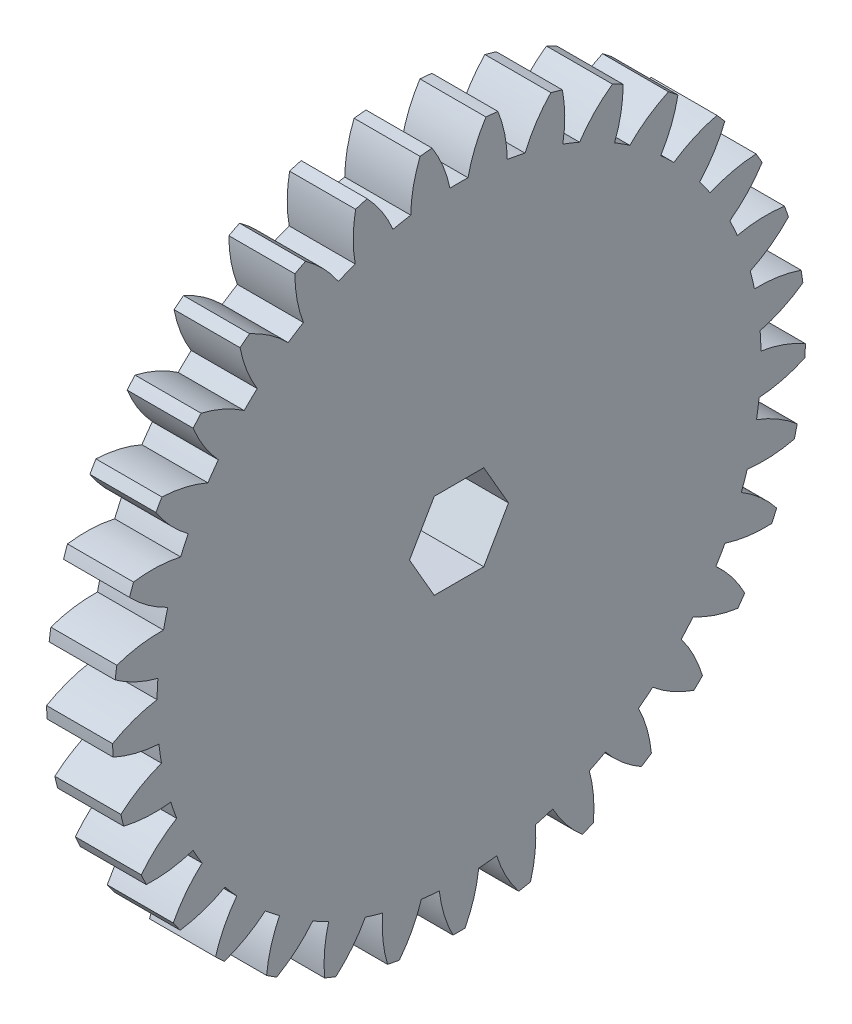
SolidWorks part; units mm, degrees
ref_plane "Plane1" through (0, 0, 0) normal (0, 0, 1) x (1, 0, 0)
ref_plane "Plane2" through (0, 0, 0) normal (0, 1, 0) x (1, 0, 0)
ref_plane "Plane3" through (0, 0, 0) normal (1, 0, 0) x (0, 0, -1)
sketch "HoldingSke" plane through (0, 0, 0) normal (0, 1, 0) x (1, 0, 0)
  line L0 (0, 0) -> (0.5591, -0.3631)
  line L1 (-15, 0) -> (100, 0) construction
  line L2 (0, 0) -> (-2.1039, 2.3779)
  line L3 (0, 0) -> (-11.863, 4.5341)
  line L4 (0, 0) -> (7.2428, 4.7035)
  line L5 (0, 0) -> (-46.8476, -17.4728)
  line L6 (0, 0) -> (-4.1448, -2.7965)
  line L7 (-2.1039, 2.3779) -> (8.6586, 51.2059)
  line L8 (-76.2, 54.61) -> (-75.3, 54.61)
  line L9 (-71.009, 38.7566) -> (-53.1078, 45.2721)
  line L10 (-76.2, 71.12) -> (104.1128, 71.12)
  line L11 (0, 0) -> (-5, 0)
  line L12 (-76.2, 101.6) -> (-76.147, 101.6)
  line L13 (24.9733, 27.94) -> (52.9518, 28.4284)
  line L14 (24.9733, 27.94) -> (24.9743, 27.94)
  line L15 (24.9733, 27.94) -> (100.4006, 29.5858)
  line L16 (-63.627, -1.5) -> (-12.827, -1.5)
  circle A0 centre (0, 0) radius 2.5
  circle A1 centre (0, 0) radius 22.874
  circle A2 centre (0, 0) radius 37.5
  circle A3 centre (0, 0) radius 2.5
  dimension "MHD" = 45.748
  dimension "Hub_dia" = 75
  dimension "Bore" = 5
  dimension "MBD" = 5
  dimension "Num_teeth" = 33
  dimension "Pitch" = 0.6667
  dimension "Overall_len" = 50
  dimension "Show_teeth" = 33
  dimension "Thickness" = 5
  dimension "OAL" = 50.0001
  dimension "T_dim" = 0.9
  dimension "Ap" = 20
  dimension "H" = 19.05
  dimension "Pitch_radius" = 180.3128
  dimension "Width" = 5
  dimension "Backlash" = 0.053
  dimension "Addendum_fac" = 1
  dimension "Dedendum_fac" = 1.25
  dimension "Clearance_fac" = 0.25
  dimension "Dedendum_add" = 0.001
  dimension "Module" = 1.5
sketch "BasProSke" plane through (0, 0, 0) normal (0, 1, 0) x (1, 0, 0)
  line L0 (-10, 0) -> (60, 0) construction
  line L1 (0, 0) -> (0, 26.25)
  line L2 (0, 0) -> (5, 0)
  line L3 (5, 0) -> (5, 26.25)
  line L4 (5, 26.25) -> (0, 26.25)
  dimension "Thickness" = 5
  dimension "Diameter" = 52.5
revolve "Base-Revolve" add sketch "BasProSke" angle 360 about L0
sketch "TooCutSke" plane through (0, 0, 0) normal (1, 0, 0) x (0, 0, -1)
  line L1 (0, 0) -> (0, 107) construction
  line L2 (0, 0) -> (-1.2704, 24.7174) construction
  line L3 (0, 0) -> (-4.7008, 49.2285) construction
  line L4 (-1.2704, 24.7174) -> (-2.3504, 24.6142) construction
  arc A0 (0.6837, 22.8638) -> (-0.6837, 22.8638) centre (0, 0) ccw
  arc A1 (2.0575, 26.1947) -> (-2.0575, 26.1947) centre (0, 0) ccw
  circle A2 centre (0, 0) radius 24.75 construction
  circle A3 centre (0, 0) radius 23.2574 construction
  arc A4 (-0.6837, 22.8638) -> (-2.0575, 26.1947) centre (-10.3699, 20.8176) ccw
  arc A5 (2.0575, 26.1947) -> (0.6837, 22.8638) centre (10.3699, 20.8176) ccw
  dimension "Root_dia" = 45.748
  dimension "Overcut_dia" = 52.5508
  dimension "Pitch_dia" = 49.5
  dimension "Base_dia" = 46.5148
  dimension "Flank_rad" = 9.9
  dimension "Half_ang" = 5.455
  dimension "Half_CT" = 1.0849
extrude "ToothCut" cut sketch "TooCutSke" along normal through all
fillet "Breaks" [suppressed] radius 0.03 tangent propagation no
fillet "RootFillets" [suppressed] radius 0.376
pattern_circular "TeethCuts" count 33 every 10.909 about axis through (-10, 0, 0) along (1, 0, 0) of "ToothCut", "RootFillets", "Breaks"
sketch "HubNeaOneSke" plane through (0, 0, 0) normal (-1, 0, 0) x (0, 0, 1)
  circle A0 centre (0, 0) radius 22.874
  dimension "Diameter" = 45.748
extrude "HubNearOne" [suppressed] add sketch "HubNeaOneSke" along normal blind 45.0001
sketch "HubNeaBotSke" plane through (0, 0, 0) normal (-1, 0, 0) x (0, 0, 1)
  circle A0 centre (0, 0) radius 22.874
  dimension "Diameter" = 45.748
extrude "HubNearBoth" [suppressed] add sketch "HubNeaBotSke" along normal blind 22.5
ref_plane "FarPln" through (5, 0, 0) normal (1, 0, 0) x (0, 0, -1)
sketch "HubFarSke" plane through (5, 0, 0) normal (1, 0, 0) x (0, 0, -1)
  circle A0 centre (0, 0) radius 22.874
  dimension "Diameter" = 45.748
extrude "HubFar" [suppressed] add sketch "HubFarSke" along normal blind 22.5
sketch "BorSke" plane through (0, 0, 0) normal (1, 0, 0) x (0, 0, -1)
  line L1 (-3.75, 0) -> (-1.875, -3.2476)
  line L2 (-1.875, -3.2476) -> (1.875, -3.2476)
  line L3 (1.875, -3.2476) -> (3.75, 0)
  line L4 (3.75, 0) -> (1.875, 3.2476)
  line L5 (1.875, 3.2476) -> (-1.875, 3.2476)
  line L6 (-1.875, 3.2476) -> (-3.75, 0)
  circle A0 centre (0, 0) radius 3.75 construction
  circle A1 centre (0, 0) radius 3.2476 construction
  dimension "Diameter" = 7.5
extrude "Bore" cut sketch "BorSke" along normal mid plane 100.0001
sketch "KeySke" plane through (0, 0, 0) normal (1, 0, 0) x (0, 0, -1)
  line L0 (-1, 0) -> (-1, 3.4)
  line L1 (-1, 3.4) -> (1, 3.4)
  line L2 (1, 3.4) -> (1, 0)
  line L3 (0, 0) -> (0, 34) construction
  line L4 (-1, 0) -> (1, 0)
  dimension "Offset" = 3.4
  dimension "Width" = 2
extrude "Keyway" [suppressed] cut sketch "KeySke" along normal mid plane 100.0001
pattern_circular "Keyway2" [suppressed] count 2 every 90 about axis through (-10, 0, 0) along (1, 0, 0) reverse direction yes
sketch "Sketch1" plane through (0, 0, 0) normal (-1, 0, 0) x (0, 0, 1)
  line L0 (-1.875, -3.2476) -> (1.875, -3.2476) construction
  line L1 (-3.75, 0) -> (-1.875, -3.2476) construction
  line L2 (-1.875, 3.2476) -> (-3.75, 0) construction
  line L3 (1.875, 3.2476) -> (-1.875, 3.2476) construction
  line L4 (3.75, 0) -> (1.875, 3.2476) construction
  line L5 (1.875, -3.2476) -> (3.75, 0) construction
  line L6 (3.75, 0) -> (1.875, 3.2476)
  line L7 (1.875, 3.2476) -> (-1.875, 3.2476)
  line L8 (-1.875, 3.2476) -> (-3.75, 0)
  line L9 (-3.75, 0) -> (-1.875, -3.2476)
  line L10 (-1.875, -3.2476) -> (1.875, -3.2476)
  line L11 (1.875, -3.2476) -> (3.75, 0)
  arc A80 (0.1868, -8.9981) -> (0.8757, -5.5554) centre (-1.8542, -6.7994) ccw
  arc A81 (-0.1868, -8.9981) -> (0.1868, -8.9981) centre (0, 0) ccw
  arc A82 (-0.8757, -5.5554) -> (-0.1868, -8.9981) centre (1.8542, -6.7994) ccw
  arc A83 (-2.5569, -5.0091) -> (-0.8757, -5.5554) centre (0, 0) ccw
  arc A84 (-5.1378, -7.3894) -> (-2.5569, -5.0091) centre (-5.4967, -4.4109) ccw
  arc A85 (-5.4401, -7.1698) -> (-5.1378, -7.3894) centre (0, 0) ccw
  arc A86 (-3.9738, -3.9797) -> (-5.4401, -7.1698) centre (-2.4965, -6.5907) ccw
  arc A87 (-5.0129, -2.5496) -> (-3.9738, -3.9797) centre (0, 0) ccw
  arc A88 (-8.4999, -2.9582) -> (-5.0129, -2.5496) centre (-7.0396, -0.3377) ccw
  arc A89 (-8.6154, -2.6029) -> (-8.4999, -2.9582) centre (0, 0) ccw
  arc A90 (-5.5541, -0.8839) -> (-8.6154, -2.6029) centre (-5.8936, -3.8646) ccw
  arc A91 (-5.5541, 0.8839) -> (-5.5541, -0.8839) centre (0, 0) ccw
  arc A92 (-8.6154, 2.6029) -> (-5.5541, 0.8839) centre (-5.8936, 3.8646) ccw
  arc A93 (-8.4999, 2.9582) -> (-8.6154, 2.6029) centre (0, 0) ccw
  arc A94 (-5.0129, 2.5496) -> (-8.4999, 2.9582) centre (-7.0396, 0.3377) ccw
  arc A95 (-3.9738, 3.9797) -> (-5.0129, 2.5496) centre (0, 0) ccw
  arc A96 (-5.4401, 7.1698) -> (-3.9738, 3.9797) centre (-2.4965, 6.5907) ccw
  arc A97 (-5.1378, 7.3894) -> (-5.4401, 7.1698) centre (0, 0) ccw
  arc A98 (-2.5569, 5.0091) -> (-5.1378, 7.3894) centre (-5.4967, 4.4109) ccw
  arc A99 (-0.8757, 5.5554) -> (-2.5569, 5.0091) centre (0, 0) ccw
  arc A100 (-0.1868, 8.9981) -> (-0.8757, 5.5554) centre (1.8542, 6.7994) ccw
  arc A101 (0.1868, 8.9981) -> (-0.1868, 8.9981) centre (0, 0) ccw
  arc A102 (0.8757, 5.5554) -> (0.1868, 8.9981) centre (-1.8542, 6.7994) ccw
  arc A103 (2.5569, 5.0091) -> (0.8757, 5.5554) centre (0, 0) ccw
  arc A104 (5.1378, 7.3894) -> (2.5569, 5.0091) centre (5.4967, 4.4109) ccw
  arc A105 (5.4401, 7.1698) -> (5.1378, 7.3894) centre (0, 0) ccw
  arc A106 (3.9738, 3.9797) -> (5.4401, 7.1698) centre (2.4965, 6.5907) ccw
  arc A107 (5.0129, 2.5496) -> (3.9738, 3.9797) centre (0, 0) ccw
  arc A108 (8.4999, 2.9582) -> (5.0129, 2.5496) centre (7.0396, 0.3377) ccw
  arc A109 (8.6154, 2.6029) -> (8.4999, 2.9582) centre (0, 0) ccw
  arc A110 (5.5541, 0.8839) -> (8.6154, 2.6029) centre (5.8936, 3.8646) ccw
  arc A111 (5.5541, -0.8839) -> (5.5541, 0.8839) centre (0, 0) ccw
  arc A112 (8.6154, -2.6029) -> (5.5541, -0.8839) centre (5.8936, -3.8646) ccw
  arc A113 (8.4999, -2.9582) -> (8.6154, -2.6029) centre (0, 0) ccw
  arc A114 (5.0129, -2.5496) -> (8.4999, -2.9582) centre (7.0396, -0.3377) ccw
  arc A115 (3.9738, -3.9797) -> (5.0129, -2.5496) centre (0, 0) ccw
  arc A116 (5.4401, -7.1698) -> (3.9738, -3.9797) centre (2.4965, -6.5907) ccw
  arc A117 (5.1378, -7.3894) -> (5.4401, -7.1698) centre (0, 0) ccw
  arc A118 (2.5569, -5.0091) -> (5.1378, -7.3894) centre (5.4967, -4.4109) ccw
  arc A119 (0.8757, -5.5554) -> (2.5569, -5.0091) centre (0, 0) ccw
extrude "Boss-Extrude1" add sketch "Sketch1" along normal blind 6
equation "' \"Module@HoldingSke\" = 6.35"
equation "' \"Num_teeth@HoldingSke\" = 12"
equation "' \"Ap@HoldingSke\" =  20"
equation "' \"Ap@HoldingSke\" = 20"
equation "' \"Width@HoldingSke\" = 0.5 * 25.4"
equation "' \"Hub_dia@HoldingSke\"= 1 * 25.4"
equation "' \"Hub_dia@HoldingSke\" = 1 * 25.4"
equation "' \"Overall_len@HoldingSke\" = 1.0 * 25.4"
equation "' \"Bore@HoldingSke\" = 0.75 * 25.4"
equation "' \"T_dim@HoldingSke\" = 0.1 * 25.4"
equation "' \"Width@KeySke\" = 0.25 * 25.4"
equation "' \"Show_teeth@HoldingSke\" = 13"
equation "' \"Backlash@HoldingSke\" = 0.009 * 25.4"
equation "' \"Addendum_fac@HoldingSke\" = 1.0"
equation "' \"Dedendum_fac@HoldingSke\" = 1.25"
equation "' \"Dedendum_add@HoldingSke\" = 0.00005 * 25.4"
equation "' \"Clearance_fac@HoldingSke\" = 0.25"
equation "\"Pitch@HoldingSke\" = 1 / \"Module@HoldingSke\""
equation "\"Overcut_dia@TooCutSke\" = (\"Num_teeth@HoldingSke\" + 2 * \"Addendum_fac@HoldingSke\") / \"Pitch@HoldingSke\" + 0.002 * 25.4"
equation "\"Pitch_dia@TooCutSke\" = \"Num_teeth@HoldingSke\" / \"Pitch@HoldingSke\""
equation "\"Base_dia@TooCutSke\" = \"Num_teeth@HoldingSke\" / \"Pitch@HoldingSke\" * cos((\"Ap@HoldingSke\"  * 3.14159265 / 180))"
equation "\"Root_dia@TooCutSke\" = (\"Num_teeth@HoldingSke\" + 2) / \"Pitch@HoldingSke\" - 2 * (\"Addendum_fac@HoldingSke\" + \"Dedendum_fac@HoldingSke\") / \"Pitch@HoldingSke\" - \"Dedendum_add@HoldingSke\" * 2"
equation "\"Half_ang@TooCutSke\" = 180 / \"Num_teeth@HoldingSke\""
equation "\"Half_CT@TooCutSke\" = \"Num_teeth@HoldingSke\" / \"Pitch@HoldingSke\" * sin((3.14159265 / 2 / \"Num_teeth@HoldingSke\")) / 2 - 7 * \"Backlash@HoldingSke\" / 4"
equation "\"Flank_rad@TooCutSke\" = \"Num_teeth@HoldingSke\" / \"Pitch@HoldingSke\" / 5"
equation "\"Radius@RootFillets\" = \"Clearance_fac@HoldingSke\" / \"Pitch@HoldingSke\" + \"Dedendum_add@HoldingSke\""
equation "\"Break_rad@Breaks\" = 0.02 / \"Pitch@HoldingSke\""
equation "\"Thickness@HoldingSke\" = \"Width@HoldingSke\""
equation "\"OAL@HoldingSke\" = \"Thickness@HoldingSke\""
equation "\"MHD@HoldingSke\" = (\"Num_teeth@HoldingSke\" + 2) / \"Pitch@HoldingSke\" - 2 * (\"Addendum_fac@HoldingSke\" + \"Dedendum_fac@HoldingSke\")  / \"Pitch@HoldingSke\" - \"Dedendum_add@HoldingSke\" * 2"
equation "\"MBD@HoldingSke\" = (\"Num_teeth@HoldingSke\" + 2) / \"Pitch@HoldingSke\" - 2 * (\"Addendum_fac@HoldingSke\" + \"Dedendum_fac@HoldingSke\")  / \"Pitch@HoldingSke\" - \"Dedendum_add@HoldingSke\" * 2 - 0.002 * 25.4"
equation "\"MHD@HoldingSke\" = ((sgn( \"MHD@HoldingSke\" - \"Hub_dia@HoldingSke\" )-1)*( \"MHD@HoldingSke\" - \"Hub_dia@HoldingSke\" ))/-2+ \"Hub_dia@HoldingSke\""
equation "\"MBD@HoldingSke\" = ((sgn( \"MBD@HoldingSke\" - \"Bore@HoldingSke\" )-1)*( \"MBD@HoldingSke\" - \"Bore@HoldingSke\" ))/-2+ \"Bore@HoldingSke\""
equation "\"OAL@HoldingSke\" = ((sgn( \"OAL@HoldingSke\" - \"Overall_len@HoldingSke\" )+1)*( \"OAL@HoldingSke\" - \"Overall_len@HoldingSke\" ))/2 + \"Overall_len@HoldingSke\" + 0.000002 * 25.4"
equation "\"Num_teeth@TeethCuts\" = int( \"Show_teeth@HoldingSke\" ) + 1"
equation "\"Num_teeth@TeethCuts\" = ((sgn( \"Num_teeth@TeethCuts\" - \"Num_teeth@HoldingSke\" )-1)*( \"Num_teeth@TeethCuts\" - \"Num_teeth@HoldingSke\" ))/-2+ \"Num_teeth@HoldingSke\""
equation "\"Num_teeth@TeethCuts\" = ((sgn( \"Num_teeth@TeethCuts\" - 2.0)+1)*( \"Num_teeth@TeethCuts\" - 2.0))/2 +2.0"
equation "\"Angle@TeethCuts\" = 360.0 / \"Num_teeth@HoldingSke\""
equation "\"Diameter@BasProSke\" = (\"Num_teeth@HoldingSke\" + 2 * \"Addendum_fac@HoldingSke\") / \"Pitch@HoldingSke\""
equation "\"Thickness@BasProSke\"  = \"Thickness@HoldingSke\""
equation "' \"Fillet_rad@BasProSke\" =  \"Thickness@HoldingSke\" * 0.05"
equation "' \"Fillet_rad@BasProSke\" = \"Thickness@HoldingSke\" * 0.05"
equation "\"MHD@HoldingSke\" = ((sgn( \"MHD@HoldingSke\" - \"Root_dia@TooCutSke\" )-1)*( \"MHD@HoldingSke\" - \"Root_dia@TooCutSke\" ))/-2+ \"Root_dia@TooCutSke\""
equation "\"Diameter@HubNeaOneSke\" = \"MHD@HoldingSke\""
equation "\"Length@HubNearOne\" = \"OAL@HoldingSke\" - \"Thickness@BasProSke\""
equation "\"Diameter@HubNeaBotSke\" = \"MHD@HoldingSke\""
equation "\"Length@HubNearBoth\" = ( \"OAL@HoldingSke\" - \"Thickness@BasProSke\" ) / 2.0"
equation "\"Thickness@FarPln\" = \"Thickness@BasProSke\""
equation "\"Diameter@HubFarSke\" = \"MHD@HoldingSke\""
equation "\"Length@HubFar\" = ( \"OAL@HoldingSke\" - \"Thickness@BasProSke\" ) / 2.0"
equation "\"Diameter@BorSke\"=7.5"
equation "\"D1@Bore\" = \"OAL@HoldingSke\" * 2.0"
equation "\"D1@Keyway\" = \"OAL@HoldingSke\" * 2.0"
equation "\"Offset@KeySke\" = \"T_dim@HoldingSke\" + \"MBD@HoldingSke\" / 2.0"
